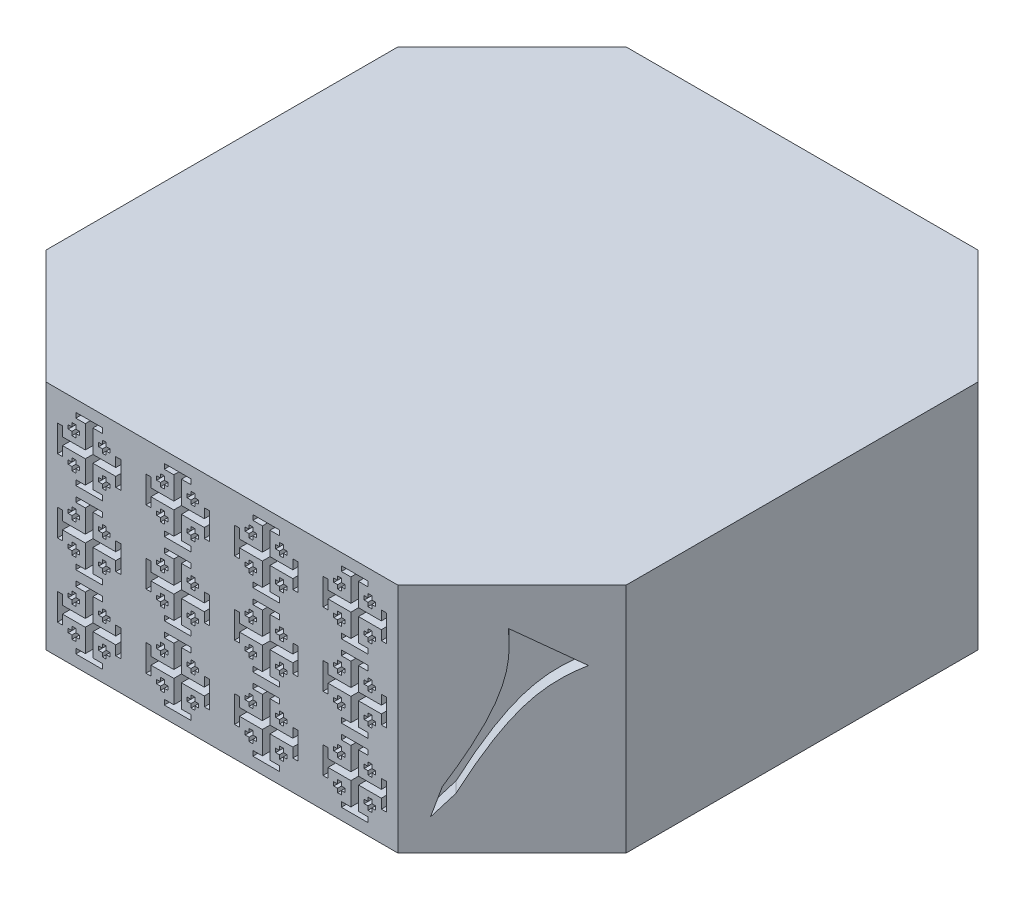
SolidWorks part; units mm, degrees
ref_plane "Front Plane" through (0, 0, 0) normal (0, 0, 1) x (1, 0, 0)
ref_plane "Top Plane" through (0, 0, 0) normal (0, 1, 0) x (1, 0, 0)
ref_plane "Right Plane" through (0, 0, 0) normal (1, 0, 0) x (0, 0, -1)
sketch "Sketch1" plane through (0, 0, 0) normal (0, 1, 0) x (1, 0, 0)
  line L1 (0, 0) -> (38.1, 0)
  line L2 (0, 0) -> (0, 38.1)
  line L3 (0, 38.1) -> (38.1, 38.1)
  line L4 (38.1, 0) -> (38.1, 38.1)
  dimension "D1" = 38.1
extrude "Boss-Extrude1" add sketch "Sketch1" along normal blind 15.24
sketch "Sketch2" plane through (0, 15.24, 0) normal (0, 1, 0) x (1, 0, 0)
  line L0 (0, 19.05) -> (38.1, 19.05) construction
  line L1 (0, 38.1) -> (0, 0) construction
  line L2 (38.1, 0) -> (38.1, 38.1) construction
  line L15 (38.1, 30.6) -> (30.6, 38.1)
  line L33 (38.1, 7.5) -> (30.6, 0)
  line L34 (7.5, 0) -> (0, 7.5)
  line L35 (7.5, 38.1) -> (0, 30.6)
  line L36 (38.1, 7.5) -> (38.1, 0)
  line L37 (38.1, 0) -> (30.6, 0)
  line L38 (38.1, 30.6) -> (38.1, 38.1)
  line L39 (38.1, 38.1) -> (30.6, 38.1)
  line L40 (7.5, 38.1) -> (0, 38.1)
  line L41 (0, 38.1) -> (0, 30.6)
  line L42 (0, 7.5) -> (0, 0)
  line L43 (0, 0) -> (7.5, 0)
  dimension "D1" = 7.5
extrude "Cut-Extrude1" cut sketch "Sketch2" against normal through all
ref_plane "Plane1" through (30.6, 0, 0) normal (1, 0, 0) x (0, 1, 0)
sketch "Sketch6" plane through (15.3, 0, 15.3) normal (0.7071, 0, 0.7071) x (0.7071, 0, -0.7071)
  line L5 (24.3455, 3.4034) -> (23.1564, 2.0557)
  line L6 (23.1564, 2.0557) -> (28.6316, 11.7194) construction
  line L7 (23.1564, 2.0557) -> (23.7012, 3.7684)
  line L8 (26.7727, 12.7726) -> (30.4906, 10.6661)
  spline S0 degree 3 poles (23.7012, 3.7684) (26.7187, 8.6625) (26.935, 10.6258) (26.7727, 12.7726) knots 0 0 0 0 1 1 1 1
  spline S1 degree 3 poles (24.3455, 3.4034) (26.9928, 8.5072) (28.5656, 9.7019) (30.4906, 10.6661) knots 0 0 0 0 1 1 1 1
  point P2 (23.2245, 2.2699)
  point P3 (28.6316, 11.7194)
extrude "Cut-Extrude2" cut sketch "Sketch6" against normal blind 1
sketch "Sketch9" plane through (0, 0, 0) normal (0, 0, 1) x (1, 0, 0)
  line L0 (9.205, 13.785) -> (9.205, 13.535)
  line L1 (9.205, 13.535) -> (8.955, 13.535)
  line L2 (8.955, 13.535) -> (8.955, 13.285)
  line L3 (8.955, 13.285) -> (9.205, 13.285)
  line L4 (9.205, 13.285) -> (9.205, 13.035)
  line L5 (9.205, 13.035) -> (9.455, 13.035)
  line L6 (9.455, 13.035) -> (9.455, 13.285)
  line L7 (9.455, 13.285) -> (9.705, 13.285)
  line L8 (9.705, 13.285) -> (9.705, 13.535)
  line L9 (9.705, 13.535) -> (9.455, 13.535)
  line L10 (9.455, 13.535) -> (9.455, 13.785)
  line L11 (9.455, 13.785) -> (9.205, 13.785)
  line L12 (10.33, 15.24) -> (10.33, 9.58) construction
  line L13 (8.7012, 12.41) -> (14.617, 12.41) construction
  line L14 (10.33, 14.49) -> (9.455, 14.49)
  line L15 (9.455, 14.49) -> (9.455, 14.16)
  line L16 (9.455, 14.16) -> (10.08, 14.16)
  line L17 (10.08, 14.16) -> (10.08, 12.66)
  line L18 (10.08, 12.66) -> (8.58, 12.66)
  line L19 (8.58, 12.66) -> (8.58, 13.285)
  line L20 (8.58, 13.285) -> (8.25, 13.285)
  line L21 (8.25, 13.285) -> (8.25, 12.41)
  line L22 (11.705, 13.285) -> (11.705, 13.535)
  line L23 (10.08, 13.41) -> (8.955, 13.41) construction
  line L24 (9.33, 12.66) -> (9.33, 13.785) construction
  line L25 (7.5, 15.24) -> (30.6, 15.24) construction
  line L26 (11.705, 13.535) -> (11.455, 13.535)
  line L27 (11.455, 13.535) -> (11.455, 13.785)
  line L28 (11.455, 13.785) -> (11.205, 13.785)
  line L29 (11.205, 13.785) -> (11.205, 13.535)
  line L30 (11.205, 13.535) -> (10.955, 13.535)
  line L31 (10.955, 13.535) -> (10.955, 13.285)
  line L32 (10.955, 13.285) -> (11.205, 13.285)
  line L33 (11.205, 13.285) -> (11.205, 13.035)
  line L34 (11.205, 13.035) -> (11.455, 13.035)
  line L35 (11.455, 13.035) -> (11.455, 13.285)
  line L36 (11.455, 13.285) -> (11.705, 13.285)
  line L37 (10.58, 12.66) -> (10.58, 14.16)
  line L38 (10.58, 14.16) -> (11.205, 14.16)
  line L39 (11.205, 14.16) -> (11.205, 14.49)
  line L40 (11.205, 14.49) -> (10.33, 14.49)
  line L41 (12.08, 12.66) -> (10.58, 12.66)
  line L42 (12.08, 13.285) -> (12.08, 12.66)
  line L43 (12.41, 13.285) -> (12.08, 13.285)
  line L44 (12.41, 12.41) -> (12.41, 13.285)
  line L45 (11.205, 11.035) -> (11.455, 11.035)
  line L46 (11.455, 11.035) -> (11.455, 11.285)
  line L47 (11.455, 11.285) -> (11.705, 11.285)
  line L48 (11.705, 11.285) -> (11.705, 11.535)
  line L49 (11.705, 11.535) -> (11.455, 11.535)
  line L50 (11.455, 11.535) -> (11.455, 11.785)
  line L51 (11.455, 11.785) -> (11.205, 11.785)
  line L52 (11.205, 11.785) -> (11.205, 11.535)
  line L53 (11.205, 11.535) -> (10.955, 11.535)
  line L54 (10.955, 11.535) -> (10.955, 11.285)
  line L55 (10.955, 11.285) -> (11.205, 11.285)
  line L56 (11.205, 11.285) -> (11.205, 11.035)
  line L57 (10.58, 12.16) -> (12.08, 12.16)
  line L58 (12.08, 12.16) -> (12.08, 11.535)
  line L59 (12.08, 11.535) -> (12.41, 11.535)
  line L60 (12.41, 11.535) -> (12.41, 12.41)
  line L61 (10.58, 10.66) -> (10.58, 12.16)
  line L62 (11.205, 10.66) -> (10.58, 10.66)
  line L63 (11.205, 10.33) -> (11.205, 10.66)
  line L64 (10.33, 10.33) -> (11.205, 10.33)
  line L65 (8.955, 11.535) -> (8.955, 11.285)
  line L66 (8.955, 11.285) -> (9.205, 11.285)
  line L67 (9.205, 11.285) -> (9.205, 11.035)
  line L68 (9.205, 11.035) -> (9.455, 11.035)
  line L69 (9.455, 11.035) -> (9.455, 11.285)
  line L70 (9.455, 11.285) -> (9.705, 11.285)
  line L71 (9.705, 11.285) -> (9.705, 11.535)
  line L72 (9.705, 11.535) -> (9.455, 11.535)
  line L73 (9.455, 11.535) -> (9.455, 11.785)
  line L74 (9.455, 11.785) -> (9.205, 11.785)
  line L75 (9.205, 11.785) -> (9.205, 11.535)
  line L76 (9.205, 11.535) -> (8.955, 11.535)
  line L77 (10.08, 12.16) -> (10.08, 10.66)
  line L78 (10.08, 10.66) -> (9.455, 10.66)
  line L79 (9.455, 10.66) -> (9.455, 10.33)
  line L80 (9.455, 10.33) -> (10.33, 10.33)
  line L81 (8.58, 12.16) -> (10.08, 12.16)
  line L82 (8.58, 11.535) -> (8.58, 12.16)
  line L83 (8.25, 11.535) -> (8.58, 11.535)
  line L84 (8.25, 12.41) -> (8.25, 11.535)
  line L85 (16.1433, 14.49) -> (15.2683, 14.49)
  line L86 (15.2683, 14.49) -> (15.2683, 14.16)
  line L87 (15.2683, 14.16) -> (15.8933, 14.16)
  line L88 (15.8933, 14.16) -> (15.8933, 12.66)
  line L89 (15.8933, 12.66) -> (14.3933, 12.66)
  line L90 (14.3933, 12.66) -> (14.3933, 13.285)
  line L91 (14.3933, 13.285) -> (14.0633, 13.285)
  line L92 (14.0633, 13.285) -> (14.0633, 12.41)
  line L93 (14.0633, 12.41) -> (14.0633, 11.535)
  line L94 (14.0633, 11.535) -> (14.3933, 11.535)
  line L95 (14.3933, 11.535) -> (14.3933, 12.16)
  line L96 (14.3933, 12.16) -> (15.8933, 12.16)
  line L97 (15.8933, 12.16) -> (15.8933, 10.66)
  line L98 (15.8933, 10.66) -> (15.2683, 10.66)
  line L99 (15.2683, 10.66) -> (15.2683, 10.33)
  line L100 (15.2683, 10.33) -> (16.1433, 10.33)
  line L101 (16.1433, 10.33) -> (17.0183, 10.33)
  line L102 (17.0183, 10.33) -> (17.0183, 10.66)
  line L103 (17.0183, 10.66) -> (16.3933, 10.66)
  line L104 (16.3933, 10.66) -> (16.3933, 12.16)
  line L105 (16.3933, 12.16) -> (17.8933, 12.16)
  line L106 (17.8933, 12.16) -> (17.8933, 11.535)
  line L107 (17.8933, 11.535) -> (18.2233, 11.535)
  line L108 (18.2233, 11.535) -> (18.2233, 12.41)
  line L109 (18.2233, 12.41) -> (18.2233, 13.285)
  line L110 (18.2233, 13.285) -> (17.8933, 13.285)
  line L111 (17.8933, 13.285) -> (17.8933, 12.66)
  line L112 (17.8933, 12.66) -> (16.3933, 12.66)
  line L113 (16.3933, 12.66) -> (16.3933, 14.16)
  line L114 (16.3933, 14.16) -> (17.0183, 14.16)
  line L115 (17.0183, 14.16) -> (17.0183, 14.49)
  line L116 (17.0183, 14.49) -> (16.1433, 14.49)
  line L117 (15.2683, 13.785) -> (15.0183, 13.785)
  line L118 (15.0183, 13.785) -> (15.0183, 13.535)
  line L119 (15.0183, 13.535) -> (14.7683, 13.535)
  line L120 (14.7683, 13.535) -> (14.7683, 13.285)
  line L121 (14.7683, 13.285) -> (15.0183, 13.285)
  line L122 (15.0183, 13.285) -> (15.0183, 13.035)
  line L123 (15.0183, 13.035) -> (15.2683, 13.035)
  line L124 (15.2683, 13.035) -> (15.2683, 13.285)
  line L125 (15.2683, 13.285) -> (15.5183, 13.285)
  line L126 (15.5183, 13.285) -> (15.5183, 13.535)
  line L127 (15.5183, 13.535) -> (15.2683, 13.535)
  line L128 (15.2683, 13.535) -> (15.2683, 13.785)
  line L129 (14.7683, 11.535) -> (14.7683, 11.285)
  line L130 (14.7683, 11.285) -> (15.0183, 11.285)
  line L131 (15.0183, 11.285) -> (15.0183, 11.035)
  line L132 (15.0183, 11.035) -> (15.2683, 11.035)
  line L133 (15.2683, 11.035) -> (15.2683, 11.285)
  line L134 (15.2683, 11.285) -> (15.5183, 11.285)
  line L135 (15.5183, 11.285) -> (15.5183, 11.535)
  line L136 (15.5183, 11.535) -> (15.2683, 11.535)
  line L137 (15.2683, 11.535) -> (15.2683, 11.785)
  line L138 (15.2683, 11.785) -> (15.0183, 11.785)
  line L139 (15.0183, 11.785) -> (15.0183, 11.535)
  line L140 (15.0183, 11.535) -> (14.7683, 11.535)
  line L141 (17.0183, 11.035) -> (17.2683, 11.035)
  line L142 (17.2683, 11.035) -> (17.2683, 11.285)
  line L143 (17.2683, 11.285) -> (17.5183, 11.285)
  line L144 (17.5183, 11.285) -> (17.5183, 11.535)
  line L145 (17.5183, 11.535) -> (17.2683, 11.535)
  line L146 (17.2683, 11.535) -> (17.2683, 11.785)
  line L147 (17.2683, 11.785) -> (17.0183, 11.785)
  line L148 (17.0183, 11.785) -> (17.0183, 11.535)
  line L149 (17.0183, 11.535) -> (16.7683, 11.535)
  line L150 (16.7683, 11.535) -> (16.7683, 11.285)
  line L151 (16.7683, 11.285) -> (17.0183, 11.285)
  line L152 (17.0183, 11.285) -> (17.0183, 11.035)
  line L153 (17.5183, 13.285) -> (17.5183, 13.535)
  line L154 (17.5183, 13.535) -> (17.2683, 13.535)
  line L155 (17.2683, 13.535) -> (17.2683, 13.785)
  line L156 (17.2683, 13.785) -> (17.0183, 13.785)
  line L157 (17.0183, 13.785) -> (17.0183, 13.535)
  line L158 (17.0183, 13.535) -> (16.7683, 13.535)
  line L159 (16.7683, 13.535) -> (16.7683, 13.285)
  line L160 (16.7683, 13.285) -> (17.0183, 13.285)
  line L161 (17.0183, 13.285) -> (17.0183, 13.035)
  line L162 (17.0183, 13.035) -> (17.2683, 13.035)
  line L163 (17.2683, 13.035) -> (17.2683, 13.285)
  line L164 (17.2683, 13.285) -> (17.5183, 13.285)
  line L165 (21.9567, 14.49) -> (21.0817, 14.49)
  line L166 (21.0817, 14.49) -> (21.0817, 14.16)
  line L167 (21.0817, 14.16) -> (21.7067, 14.16)
  line L168 (21.7067, 14.16) -> (21.7067, 12.66)
  line L169 (21.7067, 12.66) -> (20.2067, 12.66)
  line L170 (20.2067, 12.66) -> (20.2067, 13.285)
  line L171 (20.2067, 13.285) -> (19.8767, 13.285)
  line L172 (19.8767, 13.285) -> (19.8767, 12.41)
  line L173 (19.8767, 12.41) -> (19.8767, 11.535)
  line L174 (19.8767, 11.535) -> (20.2067, 11.535)
  line L175 (20.2067, 11.535) -> (20.2067, 12.16)
  line L176 (20.2067, 12.16) -> (21.7067, 12.16)
  line L177 (21.7067, 12.16) -> (21.7067, 10.66)
  line L178 (21.7067, 10.66) -> (21.0817, 10.66)
  line L179 (21.0817, 10.66) -> (21.0817, 10.33)
  line L180 (21.0817, 10.33) -> (21.9567, 10.33)
  line L181 (21.9567, 10.33) -> (22.8317, 10.33)
  line L182 (22.8317, 10.33) -> (22.8317, 10.66)
  line L183 (22.8317, 10.66) -> (22.2067, 10.66)
  line L184 (22.2067, 10.66) -> (22.2067, 12.16)
  line L185 (22.2067, 12.16) -> (23.7067, 12.16)
  line L186 (23.7067, 12.16) -> (23.7067, 11.535)
  line L187 (23.7067, 11.535) -> (24.0367, 11.535)
  line L188 (24.0367, 11.535) -> (24.0367, 12.41)
  line L189 (24.0367, 12.41) -> (24.0367, 13.285)
  line L190 (24.0367, 13.285) -> (23.7067, 13.285)
  line L191 (23.7067, 13.285) -> (23.7067, 12.66)
  line L192 (23.7067, 12.66) -> (22.2067, 12.66)
  line L193 (22.2067, 12.66) -> (22.2067, 14.16)
  line L194 (22.2067, 14.16) -> (22.8317, 14.16)
  line L195 (22.8317, 14.16) -> (22.8317, 14.49)
  line L196 (22.8317, 14.49) -> (21.9567, 14.49)
  line L197 (21.0817, 13.785) -> (20.8317, 13.785)
  line L198 (20.8317, 13.785) -> (20.8317, 13.535)
  line L199 (20.8317, 13.535) -> (20.5817, 13.535)
  line L200 (20.5817, 13.535) -> (20.5817, 13.285)
  line L201 (20.5817, 13.285) -> (20.8317, 13.285)
  line L202 (20.8317, 13.285) -> (20.8317, 13.035)
  line L203 (20.8317, 13.035) -> (21.0817, 13.035)
  line L204 (21.0817, 13.035) -> (21.0817, 13.285)
  line L205 (21.0817, 13.285) -> (21.3317, 13.285)
  line L206 (21.3317, 13.285) -> (21.3317, 13.535)
  line L207 (21.3317, 13.535) -> (21.0817, 13.535)
  line L208 (21.0817, 13.535) -> (21.0817, 13.785)
  line L209 (20.5817, 11.535) -> (20.5817, 11.285)
  line L210 (20.5817, 11.285) -> (20.8317, 11.285)
  line L211 (20.8317, 11.285) -> (20.8317, 11.035)
  line L212 (20.8317, 11.035) -> (21.0817, 11.035)
  line L213 (21.0817, 11.035) -> (21.0817, 11.285)
  line L214 (21.0817, 11.285) -> (21.3317, 11.285)
  line L215 (21.3317, 11.285) -> (21.3317, 11.535)
  line L216 (21.3317, 11.535) -> (21.0817, 11.535)
  line L217 (21.0817, 11.535) -> (21.0817, 11.785)
  line L218 (21.0817, 11.785) -> (20.8317, 11.785)
  line L219 (20.8317, 11.785) -> (20.8317, 11.535)
  line L220 (20.8317, 11.535) -> (20.5817, 11.535)
  line L221 (22.8317, 11.035) -> (23.0817, 11.035)
  line L222 (23.0817, 11.035) -> (23.0817, 11.285)
  line L223 (23.0817, 11.285) -> (23.3317, 11.285)
  line L224 (23.3317, 11.285) -> (23.3317, 11.535)
  line L225 (23.3317, 11.535) -> (23.0817, 11.535)
  line L226 (23.0817, 11.535) -> (23.0817, 11.785)
  line L227 (23.0817, 11.785) -> (22.8317, 11.785)
  line L228 (22.8317, 11.785) -> (22.8317, 11.535)
  line L229 (22.8317, 11.535) -> (22.5817, 11.535)
  line L230 (22.5817, 11.535) -> (22.5817, 11.285)
  line L231 (22.5817, 11.285) -> (22.8317, 11.285)
  line L232 (22.8317, 11.285) -> (22.8317, 11.035)
  line L233 (23.3317, 13.285) -> (23.3317, 13.535)
  line L234 (23.3317, 13.535) -> (23.0817, 13.535)
  line L235 (23.0817, 13.535) -> (23.0817, 13.785)
  line L236 (23.0817, 13.785) -> (22.8317, 13.785)
  line L237 (22.8317, 13.785) -> (22.8317, 13.535)
  line L238 (22.8317, 13.535) -> (22.5817, 13.535)
  line L239 (22.5817, 13.535) -> (22.5817, 13.285)
  line L240 (22.5817, 13.285) -> (22.8317, 13.285)
  line L241 (22.8317, 13.285) -> (22.8317, 13.035)
  line L242 (22.8317, 13.035) -> (23.0817, 13.035)
  line L243 (23.0817, 13.035) -> (23.0817, 13.285)
  line L244 (23.0817, 13.285) -> (23.3317, 13.285)
  line L245 (27.77, 14.49) -> (26.895, 14.49)
  line L246 (26.895, 14.49) -> (26.895, 14.16)
  line L247 (26.895, 14.16) -> (27.52, 14.16)
  line L248 (27.52, 14.16) -> (27.52, 12.66)
  line L249 (27.52, 12.66) -> (26.02, 12.66)
  line L250 (26.02, 12.66) -> (26.02, 13.285)
  line L251 (26.02, 13.285) -> (25.69, 13.285)
  line L252 (25.69, 13.285) -> (25.69, 12.41)
  line L253 (25.69, 12.41) -> (25.69, 11.535)
  line L254 (25.69, 11.535) -> (26.02, 11.535)
  line L255 (26.02, 11.535) -> (26.02, 12.16)
  line L256 (26.02, 12.16) -> (27.52, 12.16)
  line L257 (27.52, 12.16) -> (27.52, 10.66)
  line L258 (27.52, 10.66) -> (26.895, 10.66)
  line L259 (26.895, 10.66) -> (26.895, 10.33)
  line L260 (26.895, 10.33) -> (27.77, 10.33)
  line L261 (27.77, 10.33) -> (28.645, 10.33)
  line L262 (28.645, 10.33) -> (28.645, 10.66)
  line L263 (28.645, 10.66) -> (28.02, 10.66)
  line L264 (28.02, 10.66) -> (28.02, 12.16)
  line L265 (28.02, 12.16) -> (29.52, 12.16)
  line L266 (29.52, 12.16) -> (29.52, 11.535)
  line L267 (29.52, 11.535) -> (29.85, 11.535)
  line L268 (29.85, 11.535) -> (29.85, 12.41)
  line L269 (29.85, 12.41) -> (29.85, 13.285)
  line L270 (29.85, 13.285) -> (29.52, 13.285)
  line L271 (29.52, 13.285) -> (29.52, 12.66)
  line L272 (29.52, 12.66) -> (28.02, 12.66)
  line L273 (28.02, 12.66) -> (28.02, 14.16)
  line L274 (28.02, 14.16) -> (28.645, 14.16)
  line L275 (28.645, 14.16) -> (28.645, 14.49)
  line L276 (28.645, 14.49) -> (27.77, 14.49)
  line L277 (26.895, 13.785) -> (26.645, 13.785)
  line L278 (26.645, 13.785) -> (26.645, 13.535)
  line L279 (26.645, 13.535) -> (26.395, 13.535)
  line L280 (26.395, 13.535) -> (26.395, 13.285)
  line L281 (26.395, 13.285) -> (26.645, 13.285)
  line L282 (26.645, 13.285) -> (26.645, 13.035)
  line L283 (26.645, 13.035) -> (26.895, 13.035)
  line L284 (26.895, 13.035) -> (26.895, 13.285)
  line L285 (26.895, 13.285) -> (27.145, 13.285)
  line L286 (27.145, 13.285) -> (27.145, 13.535)
  line L287 (27.145, 13.535) -> (26.895, 13.535)
  line L288 (26.895, 13.535) -> (26.895, 13.785)
  line L289 (26.395, 11.535) -> (26.395, 11.285)
  line L290 (26.395, 11.285) -> (26.645, 11.285)
  line L291 (26.645, 11.285) -> (26.645, 11.035)
  line L292 (26.645, 11.035) -> (26.895, 11.035)
  line L293 (26.895, 11.035) -> (26.895, 11.285)
  line L294 (26.895, 11.285) -> (27.145, 11.285)
  line L295 (27.145, 11.285) -> (27.145, 11.535)
  line L296 (27.145, 11.535) -> (26.895, 11.535)
  line L297 (26.895, 11.535) -> (26.895, 11.785)
  line L298 (26.895, 11.785) -> (26.645, 11.785)
  line L299 (26.645, 11.785) -> (26.645, 11.535)
  line L300 (26.645, 11.535) -> (26.395, 11.535)
  line L301 (28.645, 11.035) -> (28.895, 11.035)
  line L302 (28.895, 11.035) -> (28.895, 11.285)
  line L303 (28.895, 11.285) -> (29.145, 11.285)
  line L304 (29.145, 11.285) -> (29.145, 11.535)
  line L305 (29.145, 11.535) -> (28.895, 11.535)
  line L306 (28.895, 11.535) -> (28.895, 11.785)
  line L307 (28.895, 11.785) -> (28.645, 11.785)
  line L308 (28.645, 11.785) -> (28.645, 11.535)
  line L309 (28.645, 11.535) -> (28.395, 11.535)
  line L310 (28.395, 11.535) -> (28.395, 11.285)
  line L311 (28.395, 11.285) -> (28.645, 11.285)
  line L312 (28.645, 11.285) -> (28.645, 11.035)
  line L313 (29.145, 13.285) -> (29.145, 13.535)
  line L314 (29.145, 13.535) -> (28.895, 13.535)
  line L315 (28.895, 13.535) -> (28.895, 13.785)
  line L316 (28.895, 13.785) -> (28.645, 13.785)
  line L317 (28.645, 13.785) -> (28.645, 13.535)
  line L318 (28.645, 13.535) -> (28.395, 13.535)
  line L319 (28.395, 13.535) -> (28.395, 13.285)
  line L320 (28.395, 13.285) -> (28.645, 13.285)
  line L321 (28.645, 13.285) -> (28.645, 13.035)
  line L322 (28.645, 13.035) -> (28.895, 13.035)
  line L323 (28.895, 13.035) -> (28.895, 13.285)
  line L324 (28.895, 13.285) -> (29.145, 13.285)
  line L325 (16.1433, 9.7) -> (15.2683, 9.7)
  line L326 (15.2683, 9.7) -> (15.2683, 9.37)
  line L327 (15.2683, 9.37) -> (15.8933, 9.37)
  line L328 (15.8933, 9.37) -> (15.8933, 7.87)
  line L329 (15.8933, 7.87) -> (14.3933, 7.87)
  line L330 (14.3933, 7.87) -> (14.3933, 8.495)
  line L331 (14.3933, 8.495) -> (14.0633, 8.495)
  line L332 (14.0633, 8.495) -> (14.0633, 7.62)
  line L333 (14.0633, 7.62) -> (14.0633, 6.745)
  line L334 (14.0633, 6.745) -> (14.3933, 6.745)
  line L335 (14.3933, 6.745) -> (14.3933, 7.37)
  line L336 (14.3933, 7.37) -> (15.8933, 7.37)
  line L337 (15.8933, 7.37) -> (15.8933, 5.87)
  line L338 (15.8933, 5.87) -> (15.2683, 5.87)
  line L339 (15.2683, 5.87) -> (15.2683, 5.54)
  line L340 (15.2683, 5.54) -> (16.1433, 5.54)
  line L341 (16.1433, 5.54) -> (17.0183, 5.54)
  line L342 (17.0183, 5.54) -> (17.0183, 5.87)
  line L343 (17.0183, 5.87) -> (16.3933, 5.87)
  line L344 (16.3933, 5.87) -> (16.3933, 7.37)
  line L345 (16.3933, 7.37) -> (17.8933, 7.37)
  line L346 (17.8933, 7.37) -> (17.8933, 6.745)
  line L347 (17.8933, 6.745) -> (18.2233, 6.745)
  line L348 (18.2233, 6.745) -> (18.2233, 7.62)
  line L349 (18.2233, 7.62) -> (18.2233, 8.495)
  line L350 (18.2233, 8.495) -> (17.8933, 8.495)
  line L351 (17.8933, 8.495) -> (17.8933, 7.87)
  line L352 (17.8933, 7.87) -> (16.3933, 7.87)
  line L353 (16.3933, 7.87) -> (16.3933, 9.37)
  line L354 (16.3933, 9.37) -> (17.0183, 9.37)
  line L355 (17.0183, 9.37) -> (17.0183, 9.7)
  line L356 (17.0183, 9.7) -> (16.1433, 9.7)
  line L357 (15.2683, 8.995) -> (15.0183, 8.995)
  line L358 (15.0183, 8.995) -> (15.0183, 8.745)
  line L359 (15.0183, 8.745) -> (14.7683, 8.745)
  line L360 (14.7683, 8.745) -> (14.7683, 8.495)
  line L361 (14.7683, 8.495) -> (15.0183, 8.495)
  line L362 (15.0183, 8.495) -> (15.0183, 8.245)
  line L363 (15.0183, 8.245) -> (15.2683, 8.245)
  line L364 (15.2683, 8.245) -> (15.2683, 8.495)
  line L365 (15.2683, 8.495) -> (15.5183, 8.495)
  line L366 (15.5183, 8.495) -> (15.5183, 8.745)
  line L367 (15.5183, 8.745) -> (15.2683, 8.745)
  line L368 (15.2683, 8.745) -> (15.2683, 8.995)
  line L369 (14.7683, 6.745) -> (14.7683, 6.495)
  line L370 (14.7683, 6.495) -> (15.0183, 6.495)
  line L371 (15.0183, 6.495) -> (15.0183, 6.245)
  line L372 (15.0183, 6.245) -> (15.2683, 6.245)
  line L373 (15.2683, 6.245) -> (15.2683, 6.495)
  line L374 (15.2683, 6.495) -> (15.5183, 6.495)
  line L375 (15.5183, 6.495) -> (15.5183, 6.745)
  line L376 (15.5183, 6.745) -> (15.2683, 6.745)
  line L377 (15.2683, 6.745) -> (15.2683, 6.995)
  line L378 (15.2683, 6.995) -> (15.0183, 6.995)
  line L379 (15.0183, 6.995) -> (15.0183, 6.745)
  line L380 (15.0183, 6.745) -> (14.7683, 6.745)
  line L381 (17.0183, 6.245) -> (17.2683, 6.245)
  line L382 (17.2683, 6.245) -> (17.2683, 6.495)
  line L383 (17.2683, 6.495) -> (17.5183, 6.495)
  line L384 (17.5183, 6.495) -> (17.5183, 6.745)
  line L385 (17.5183, 6.745) -> (17.2683, 6.745)
  line L386 (17.2683, 6.745) -> (17.2683, 6.995)
  line L387 (17.2683, 6.995) -> (17.0183, 6.995)
  line L388 (17.0183, 6.995) -> (17.0183, 6.745)
  line L389 (17.0183, 6.745) -> (16.7683, 6.745)
  line L390 (16.7683, 6.745) -> (16.7683, 6.495)
  line L391 (16.7683, 6.495) -> (17.0183, 6.495)
  line L392 (17.0183, 6.495) -> (17.0183, 6.245)
  line L393 (17.5183, 8.495) -> (17.5183, 8.745)
  line L394 (17.5183, 8.745) -> (17.2683, 8.745)
  line L395 (17.2683, 8.745) -> (17.2683, 8.995)
  line L396 (17.2683, 8.995) -> (17.0183, 8.995)
  line L397 (17.0183, 8.995) -> (17.0183, 8.745)
  line L398 (17.0183, 8.745) -> (16.7683, 8.745)
  line L399 (16.7683, 8.745) -> (16.7683, 8.495)
  line L400 (16.7683, 8.495) -> (17.0183, 8.495)
  line L401 (17.0183, 8.495) -> (17.0183, 8.245)
  line L402 (17.0183, 8.245) -> (17.2683, 8.245)
  line L403 (17.2683, 8.245) -> (17.2683, 8.495)
  line L404 (17.2683, 8.495) -> (17.5183, 8.495)
  line L405 (21.9567, 9.7) -> (21.0817, 9.7)
  line L406 (21.0817, 9.7) -> (21.0817, 9.37)
  line L407 (21.0817, 9.37) -> (21.7067, 9.37)
  line L408 (21.7067, 9.37) -> (21.7067, 7.87)
  line L409 (21.7067, 7.87) -> (20.2067, 7.87)
  line L410 (20.2067, 7.87) -> (20.2067, 8.495)
  line L411 (20.2067, 8.495) -> (19.8767, 8.495)
  line L412 (19.8767, 8.495) -> (19.8767, 7.62)
  line L413 (19.8767, 7.62) -> (19.8767, 6.745)
  line L414 (19.8767, 6.745) -> (20.2067, 6.745)
  line L415 (20.2067, 6.745) -> (20.2067, 7.37)
  line L416 (20.2067, 7.37) -> (21.7067, 7.37)
  line L417 (21.7067, 7.37) -> (21.7067, 5.87)
  line L418 (21.7067, 5.87) -> (21.0817, 5.87)
  line L419 (21.0817, 5.87) -> (21.0817, 5.54)
  line L420 (21.0817, 5.54) -> (21.9567, 5.54)
  line L421 (21.9567, 5.54) -> (22.8317, 5.54)
  line L422 (22.8317, 5.54) -> (22.8317, 5.87)
  line L423 (22.8317, 5.87) -> (22.2067, 5.87)
  line L424 (22.2067, 5.87) -> (22.2067, 7.37)
  line L425 (22.2067, 7.37) -> (23.7067, 7.37)
  line L426 (23.7067, 7.37) -> (23.7067, 6.745)
  line L427 (23.7067, 6.745) -> (24.0367, 6.745)
  line L428 (24.0367, 6.745) -> (24.0367, 7.62)
  line L429 (24.0367, 7.62) -> (24.0367, 8.495)
  line L430 (24.0367, 8.495) -> (23.7067, 8.495)
  line L431 (23.7067, 8.495) -> (23.7067, 7.87)
  line L432 (23.7067, 7.87) -> (22.2067, 7.87)
  line L433 (22.2067, 7.87) -> (22.2067, 9.37)
  line L434 (22.2067, 9.37) -> (22.8317, 9.37)
  line L435 (22.8317, 9.37) -> (22.8317, 9.7)
  line L436 (22.8317, 9.7) -> (21.9567, 9.7)
  line L437 (21.0817, 8.995) -> (20.8317, 8.995)
  line L438 (20.8317, 8.995) -> (20.8317, 8.745)
  line L439 (20.8317, 8.745) -> (20.5817, 8.745)
  line L440 (20.5817, 8.745) -> (20.5817, 8.495)
  line L441 (20.5817, 8.495) -> (20.8317, 8.495)
  line L442 (20.8317, 8.495) -> (20.8317, 8.245)
  line L443 (20.8317, 8.245) -> (21.0817, 8.245)
  line L444 (21.0817, 8.245) -> (21.0817, 8.495)
  line L445 (21.0817, 8.495) -> (21.3317, 8.495)
  line L446 (21.3317, 8.495) -> (21.3317, 8.745)
  line L447 (21.3317, 8.745) -> (21.0817, 8.745)
  line L448 (21.0817, 8.745) -> (21.0817, 8.995)
  line L449 (20.5817, 6.745) -> (20.5817, 6.495)
  line L450 (20.5817, 6.495) -> (20.8317, 6.495)
  line L451 (20.8317, 6.495) -> (20.8317, 6.245)
  line L452 (20.8317, 6.245) -> (21.0817, 6.245)
  line L453 (21.0817, 6.245) -> (21.0817, 6.495)
  line L454 (21.0817, 6.495) -> (21.3317, 6.495)
  line L455 (21.3317, 6.495) -> (21.3317, 6.745)
  line L456 (21.3317, 6.745) -> (21.0817, 6.745)
  line L457 (21.0817, 6.745) -> (21.0817, 6.995)
  line L458 (21.0817, 6.995) -> (20.8317, 6.995)
  line L459 (20.8317, 6.995) -> (20.8317, 6.745)
  line L460 (20.8317, 6.745) -> (20.5817, 6.745)
  line L461 (22.8317, 6.245) -> (23.0817, 6.245)
  line L462 (23.0817, 6.245) -> (23.0817, 6.495)
  line L463 (23.0817, 6.495) -> (23.3317, 6.495)
  line L464 (23.3317, 6.495) -> (23.3317, 6.745)
  line L465 (23.3317, 6.745) -> (23.0817, 6.745)
  line L466 (23.0817, 6.745) -> (23.0817, 6.995)
  line L467 (23.0817, 6.995) -> (22.8317, 6.995)
  line L468 (22.8317, 6.995) -> (22.8317, 6.745)
  line L469 (22.8317, 6.745) -> (22.5817, 6.745)
  line L470 (22.5817, 6.745) -> (22.5817, 6.495)
  line L471 (22.5817, 6.495) -> (22.8317, 6.495)
  line L472 (22.8317, 6.495) -> (22.8317, 6.245)
  line L473 (23.3317, 8.495) -> (23.3317, 8.745)
  line L474 (23.3317, 8.745) -> (23.0817, 8.745)
  line L475 (23.0817, 8.745) -> (23.0817, 8.995)
  line L476 (23.0817, 8.995) -> (22.8317, 8.995)
  line L477 (22.8317, 8.995) -> (22.8317, 8.745)
  line L478 (22.8317, 8.745) -> (22.5817, 8.745)
  line L479 (22.5817, 8.745) -> (22.5817, 8.495)
  line L480 (22.5817, 8.495) -> (22.8317, 8.495)
  line L481 (22.8317, 8.495) -> (22.8317, 8.245)
  line L482 (22.8317, 8.245) -> (23.0817, 8.245)
  line L483 (23.0817, 8.245) -> (23.0817, 8.495)
  line L484 (23.0817, 8.495) -> (23.3317, 8.495)
  line L485 (27.77, 9.7) -> (26.895, 9.7)
  line L486 (26.895, 9.7) -> (26.895, 9.37)
  line L487 (26.895, 9.37) -> (27.52, 9.37)
  line L488 (27.52, 9.37) -> (27.52, 7.87)
  line L489 (27.52, 7.87) -> (26.02, 7.87)
  line L490 (26.02, 7.87) -> (26.02, 8.495)
  line L491 (26.02, 8.495) -> (25.69, 8.495)
  line L492 (25.69, 8.495) -> (25.69, 7.62)
  line L493 (25.69, 7.62) -> (25.69, 6.745)
  line L494 (25.69, 6.745) -> (26.02, 6.745)
  line L495 (26.02, 6.745) -> (26.02, 7.37)
  line L496 (26.02, 7.37) -> (27.52, 7.37)
  line L497 (27.52, 7.37) -> (27.52, 5.87)
  line L498 (27.52, 5.87) -> (26.895, 5.87)
  line L499 (26.895, 5.87) -> (26.895, 5.54)
  line L500 (26.895, 5.54) -> (27.77, 5.54)
  line L501 (27.77, 5.54) -> (28.645, 5.54)
  line L502 (28.645, 5.54) -> (28.645, 5.87)
  line L503 (28.645, 5.87) -> (28.02, 5.87)
  line L504 (28.02, 5.87) -> (28.02, 7.37)
  line L505 (28.02, 7.37) -> (29.52, 7.37)
  line L506 (29.52, 7.37) -> (29.52, 6.745)
  line L507 (29.52, 6.745) -> (29.85, 6.745)
  line L508 (29.85, 6.745) -> (29.85, 7.62)
  line L509 (29.85, 7.62) -> (29.85, 8.495)
  line L510 (29.85, 8.495) -> (29.52, 8.495)
  line L511 (29.52, 8.495) -> (29.52, 7.87)
  line L512 (29.52, 7.87) -> (28.02, 7.87)
  line L513 (28.02, 7.87) -> (28.02, 9.37)
  line L514 (28.02, 9.37) -> (28.645, 9.37)
  line L515 (28.645, 9.37) -> (28.645, 9.7)
  line L516 (28.645, 9.7) -> (27.77, 9.7)
  line L517 (26.895, 8.995) -> (26.645, 8.995)
  line L518 (26.645, 8.995) -> (26.645, 8.745)
  line L519 (26.645, 8.745) -> (26.395, 8.745)
  line L520 (26.395, 8.745) -> (26.395, 8.495)
  line L521 (26.395, 8.495) -> (26.645, 8.495)
  line L522 (26.645, 8.495) -> (26.645, 8.245)
  line L523 (26.645, 8.245) -> (26.895, 8.245)
  line L524 (26.895, 8.245) -> (26.895, 8.495)
  line L525 (26.895, 8.495) -> (27.145, 8.495)
  line L526 (27.145, 8.495) -> (27.145, 8.745)
  line L527 (27.145, 8.745) -> (26.895, 8.745)
  line L528 (26.895, 8.745) -> (26.895, 8.995)
  line L529 (26.395, 6.745) -> (26.395, 6.495)
  line L530 (26.395, 6.495) -> (26.645, 6.495)
  line L531 (26.645, 6.495) -> (26.645, 6.245)
  line L532 (26.645, 6.245) -> (26.895, 6.245)
  line L533 (26.895, 6.245) -> (26.895, 6.495)
  line L534 (26.895, 6.495) -> (27.145, 6.495)
  line L535 (27.145, 6.495) -> (27.145, 6.745)
  line L536 (27.145, 6.745) -> (26.895, 6.745)
  line L537 (26.895, 6.745) -> (26.895, 6.995)
  line L538 (26.895, 6.995) -> (26.645, 6.995)
  line L539 (26.645, 6.995) -> (26.645, 6.745)
  line L540 (26.645, 6.745) -> (26.395, 6.745)
  line L541 (28.645, 6.245) -> (28.895, 6.245)
  line L542 (28.895, 6.245) -> (28.895, 6.495)
  line L543 (28.895, 6.495) -> (29.145, 6.495)
  line L544 (29.145, 6.495) -> (29.145, 6.745)
  line L545 (29.145, 6.745) -> (28.895, 6.745)
  line L546 (28.895, 6.745) -> (28.895, 6.995)
  line L547 (28.895, 6.995) -> (28.645, 6.995)
  line L548 (28.645, 6.995) -> (28.645, 6.745)
  line L549 (28.645, 6.745) -> (28.395, 6.745)
  line L550 (28.395, 6.745) -> (28.395, 6.495)
  line L551 (28.395, 6.495) -> (28.645, 6.495)
  line L552 (28.645, 6.495) -> (28.645, 6.245)
  line L553 (29.145, 8.495) -> (29.145, 8.745)
  line L554 (29.145, 8.745) -> (28.895, 8.745)
  line L555 (28.895, 8.745) -> (28.895, 8.995)
  line L556 (28.895, 8.995) -> (28.645, 8.995)
  line L557 (28.645, 8.995) -> (28.645, 8.745)
  line L558 (28.645, 8.745) -> (28.395, 8.745)
  line L559 (28.395, 8.745) -> (28.395, 8.495)
  line L560 (28.395, 8.495) -> (28.645, 8.495)
  line L561 (28.645, 8.495) -> (28.645, 8.245)
  line L562 (28.645, 8.245) -> (28.895, 8.245)
  line L563 (28.895, 8.245) -> (28.895, 8.495)
  line L564 (28.895, 8.495) -> (29.145, 8.495)
  line L565 (16.1433, 4.91) -> (15.2683, 4.91)
  line L566 (15.2683, 4.91) -> (15.2683, 4.58)
  line L567 (15.2683, 4.58) -> (15.8933, 4.58)
  line L568 (15.8933, 4.58) -> (15.8933, 3.08)
  line L569 (15.8933, 3.08) -> (14.3933, 3.08)
  line L570 (14.3933, 3.08) -> (14.3933, 3.705)
  line L571 (14.3933, 3.705) -> (14.0633, 3.705)
  line L572 (14.0633, 3.705) -> (14.0633, 2.83)
  line L573 (14.0633, 2.83) -> (14.0633, 1.955)
  line L574 (14.0633, 1.955) -> (14.3933, 1.955)
  line L575 (14.3933, 1.955) -> (14.3933, 2.58)
  line L576 (14.3933, 2.58) -> (15.8933, 2.58)
  line L577 (15.8933, 2.58) -> (15.8933, 1.08)
  line L578 (15.8933, 1.08) -> (15.2683, 1.08)
  line L579 (15.2683, 1.08) -> (15.2683, 0.75)
  line L580 (15.2683, 0.75) -> (16.1433, 0.75)
  line L581 (16.1433, 0.75) -> (17.0183, 0.75)
  line L582 (17.0183, 0.75) -> (17.0183, 1.08)
  line L583 (17.0183, 1.08) -> (16.3933, 1.08)
  line L584 (16.3933, 1.08) -> (16.3933, 2.58)
  line L585 (16.3933, 2.58) -> (17.8933, 2.58)
  line L586 (17.8933, 2.58) -> (17.8933, 1.955)
  line L587 (17.8933, 1.955) -> (18.2233, 1.955)
  line L588 (18.2233, 1.955) -> (18.2233, 2.83)
  line L589 (18.2233, 2.83) -> (18.2233, 3.705)
  line L590 (18.2233, 3.705) -> (17.8933, 3.705)
  line L591 (17.8933, 3.705) -> (17.8933, 3.08)
  line L592 (17.8933, 3.08) -> (16.3933, 3.08)
  line L593 (16.3933, 3.08) -> (16.3933, 4.58)
  line L594 (16.3933, 4.58) -> (17.0183, 4.58)
  line L595 (17.0183, 4.58) -> (17.0183, 4.91)
  line L596 (17.0183, 4.91) -> (16.1433, 4.91)
  line L597 (15.2683, 4.205) -> (15.0183, 4.205)
  line L598 (15.0183, 4.205) -> (15.0183, 3.955)
  line L599 (15.0183, 3.955) -> (14.7683, 3.955)
  line L600 (14.7683, 3.955) -> (14.7683, 3.705)
  line L601 (14.7683, 3.705) -> (15.0183, 3.705)
  line L602 (15.0183, 3.705) -> (15.0183, 3.455)
  line L603 (15.0183, 3.455) -> (15.2683, 3.455)
  line L604 (15.2683, 3.455) -> (15.2683, 3.705)
  line L605 (15.2683, 3.705) -> (15.5183, 3.705)
  line L606 (15.5183, 3.705) -> (15.5183, 3.955)
  line L607 (15.5183, 3.955) -> (15.2683, 3.955)
  line L608 (15.2683, 3.955) -> (15.2683, 4.205)
  line L609 (14.7683, 1.955) -> (14.7683, 1.705)
  line L610 (14.7683, 1.705) -> (15.0183, 1.705)
  line L611 (15.0183, 1.705) -> (15.0183, 1.455)
  line L612 (15.0183, 1.455) -> (15.2683, 1.455)
  line L613 (15.2683, 1.455) -> (15.2683, 1.705)
  line L614 (15.2683, 1.705) -> (15.5183, 1.705)
  line L615 (15.5183, 1.705) -> (15.5183, 1.955)
  line L616 (15.5183, 1.955) -> (15.2683, 1.955)
  line L617 (15.2683, 1.955) -> (15.2683, 2.205)
  line L618 (15.2683, 2.205) -> (15.0183, 2.205)
  line L619 (15.0183, 2.205) -> (15.0183, 1.955)
  line L620 (15.0183, 1.955) -> (14.7683, 1.955)
  line L621 (17.0183, 1.455) -> (17.2683, 1.455)
  line L622 (17.2683, 1.455) -> (17.2683, 1.705)
  line L623 (17.2683, 1.705) -> (17.5183, 1.705)
  line L624 (17.5183, 1.705) -> (17.5183, 1.955)
  line L625 (17.5183, 1.955) -> (17.2683, 1.955)
  line L626 (17.2683, 1.955) -> (17.2683, 2.205)
  line L627 (17.2683, 2.205) -> (17.0183, 2.205)
  line L628 (17.0183, 2.205) -> (17.0183, 1.955)
  line L629 (17.0183, 1.955) -> (16.7683, 1.955)
  line L630 (16.7683, 1.955) -> (16.7683, 1.705)
  line L631 (16.7683, 1.705) -> (17.0183, 1.705)
  line L632 (17.0183, 1.705) -> (17.0183, 1.455)
  line L633 (17.5183, 3.705) -> (17.5183, 3.955)
  line L634 (17.5183, 3.955) -> (17.2683, 3.955)
  line L635 (17.2683, 3.955) -> (17.2683, 4.205)
  line L636 (17.2683, 4.205) -> (17.0183, 4.205)
  line L637 (17.0183, 4.205) -> (17.0183, 3.955)
  line L638 (17.0183, 3.955) -> (16.7683, 3.955)
  line L639 (16.7683, 3.955) -> (16.7683, 3.705)
  line L640 (16.7683, 3.705) -> (17.0183, 3.705)
  line L641 (17.0183, 3.705) -> (17.0183, 3.455)
  line L642 (17.0183, 3.455) -> (17.2683, 3.455)
  line L643 (17.2683, 3.455) -> (17.2683, 3.705)
  line L644 (17.2683, 3.705) -> (17.5183, 3.705)
  line L645 (21.9567, 4.91) -> (21.0817, 4.91)
  line L646 (21.0817, 4.91) -> (21.0817, 4.58)
  line L647 (21.0817, 4.58) -> (21.7067, 4.58)
  line L648 (21.7067, 4.58) -> (21.7067, 3.08)
  line L649 (21.7067, 3.08) -> (20.2067, 3.08)
  line L650 (20.2067, 3.08) -> (20.2067, 3.705)
  line L651 (20.2067, 3.705) -> (19.8767, 3.705)
  line L652 (19.8767, 3.705) -> (19.8767, 2.83)
  line L653 (19.8767, 2.83) -> (19.8767, 1.955)
  line L654 (19.8767, 1.955) -> (20.2067, 1.955)
  line L655 (20.2067, 1.955) -> (20.2067, 2.58)
  line L656 (20.2067, 2.58) -> (21.7067, 2.58)
  line L657 (21.7067, 2.58) -> (21.7067, 1.08)
  line L658 (21.7067, 1.08) -> (21.0817, 1.08)
  line L659 (21.0817, 1.08) -> (21.0817, 0.75)
  line L660 (21.0817, 0.75) -> (21.9567, 0.75)
  line L661 (21.9567, 0.75) -> (22.8317, 0.75)
  line L662 (22.8317, 0.75) -> (22.8317, 1.08)
  line L663 (22.8317, 1.08) -> (22.2067, 1.08)
  line L664 (22.2067, 1.08) -> (22.2067, 2.58)
  line L665 (22.2067, 2.58) -> (23.7067, 2.58)
  line L666 (23.7067, 2.58) -> (23.7067, 1.955)
  line L667 (23.7067, 1.955) -> (24.0367, 1.955)
  line L668 (24.0367, 1.955) -> (24.0367, 2.83)
  line L669 (24.0367, 2.83) -> (24.0367, 3.705)
  line L670 (24.0367, 3.705) -> (23.7067, 3.705)
  line L671 (23.7067, 3.705) -> (23.7067, 3.08)
  line L672 (23.7067, 3.08) -> (22.2067, 3.08)
  line L673 (22.2067, 3.08) -> (22.2067, 4.58)
  line L674 (22.2067, 4.58) -> (22.8317, 4.58)
  line L675 (22.8317, 4.58) -> (22.8317, 4.91)
  line L676 (22.8317, 4.91) -> (21.9567, 4.91)
  line L677 (21.0817, 4.205) -> (20.8317, 4.205)
  line L678 (20.8317, 4.205) -> (20.8317, 3.955)
  line L679 (20.8317, 3.955) -> (20.5817, 3.955)
  line L680 (20.5817, 3.955) -> (20.5817, 3.705)
  line L681 (20.5817, 3.705) -> (20.8317, 3.705)
  line L682 (20.8317, 3.705) -> (20.8317, 3.455)
  line L683 (20.8317, 3.455) -> (21.0817, 3.455)
  line L684 (21.0817, 3.455) -> (21.0817, 3.705)
  line L685 (21.0817, 3.705) -> (21.3317, 3.705)
  line L686 (21.3317, 3.705) -> (21.3317, 3.955)
  line L687 (21.3317, 3.955) -> (21.0817, 3.955)
  line L688 (21.0817, 3.955) -> (21.0817, 4.205)
  line L689 (20.5817, 1.955) -> (20.5817, 1.705)
  line L690 (20.5817, 1.705) -> (20.8317, 1.705)
  line L691 (20.8317, 1.705) -> (20.8317, 1.455)
  line L692 (20.8317, 1.455) -> (21.0817, 1.455)
  line L693 (21.0817, 1.455) -> (21.0817, 1.705)
  line L694 (21.0817, 1.705) -> (21.3317, 1.705)
  line L695 (21.3317, 1.705) -> (21.3317, 1.955)
  line L696 (21.3317, 1.955) -> (21.0817, 1.955)
  line L697 (21.0817, 1.955) -> (21.0817, 2.205)
  line L698 (21.0817, 2.205) -> (20.8317, 2.205)
  line L699 (20.8317, 2.205) -> (20.8317, 1.955)
  line L700 (20.8317, 1.955) -> (20.5817, 1.955)
  line L701 (22.8317, 1.455) -> (23.0817, 1.455)
  line L702 (23.0817, 1.455) -> (23.0817, 1.705)
  line L703 (23.0817, 1.705) -> (23.3317, 1.705)
  line L704 (23.3317, 1.705) -> (23.3317, 1.955)
  line L705 (23.3317, 1.955) -> (23.0817, 1.955)
  line L706 (23.0817, 1.955) -> (23.0817, 2.205)
  line L707 (23.0817, 2.205) -> (22.8317, 2.205)
  line L708 (22.8317, 2.205) -> (22.8317, 1.955)
  line L709 (22.8317, 1.955) -> (22.5817, 1.955)
  line L710 (22.5817, 1.955) -> (22.5817, 1.705)
  line L711 (22.5817, 1.705) -> (22.8317, 1.705)
  line L712 (22.8317, 1.705) -> (22.8317, 1.455)
  line L713 (23.3317, 3.705) -> (23.3317, 3.955)
  line L714 (23.3317, 3.955) -> (23.0817, 3.955)
  line L715 (23.0817, 3.955) -> (23.0817, 4.205)
  line L716 (23.0817, 4.205) -> (22.8317, 4.205)
  line L717 (22.8317, 4.205) -> (22.8317, 3.955)
  line L718 (22.8317, 3.955) -> (22.5817, 3.955)
  line L719 (22.5817, 3.955) -> (22.5817, 3.705)
  line L720 (22.5817, 3.705) -> (22.8317, 3.705)
  line L721 (22.8317, 3.705) -> (22.8317, 3.455)
  line L722 (22.8317, 3.455) -> (23.0817, 3.455)
  line L723 (23.0817, 3.455) -> (23.0817, 3.705)
  line L724 (23.0817, 3.705) -> (23.3317, 3.705)
  line L725 (27.77, 4.91) -> (26.895, 4.91)
  line L726 (26.895, 4.91) -> (26.895, 4.58)
  line L727 (26.895, 4.58) -> (27.52, 4.58)
  line L728 (27.52, 4.58) -> (27.52, 3.08)
  line L729 (27.52, 3.08) -> (26.02, 3.08)
  line L730 (26.02, 3.08) -> (26.02, 3.705)
  line L731 (26.02, 3.705) -> (25.69, 3.705)
  line L732 (25.69, 3.705) -> (25.69, 2.83)
  line L733 (25.69, 2.83) -> (25.69, 1.955)
  line L734 (25.69, 1.955) -> (26.02, 1.955)
  line L735 (26.02, 1.955) -> (26.02, 2.58)
  line L736 (26.02, 2.58) -> (27.52, 2.58)
  line L737 (27.52, 2.58) -> (27.52, 1.08)
  line L738 (27.52, 1.08) -> (26.895, 1.08)
  line L739 (26.895, 1.08) -> (26.895, 0.75)
  line L740 (26.895, 0.75) -> (27.77, 0.75)
  line L741 (27.77, 0.75) -> (28.645, 0.75)
  line L742 (28.645, 0.75) -> (28.645, 1.08)
  line L743 (28.645, 1.08) -> (28.02, 1.08)
  line L744 (28.02, 1.08) -> (28.02, 2.58)
  line L745 (28.02, 2.58) -> (29.52, 2.58)
  line L746 (29.52, 2.58) -> (29.52, 1.955)
  line L747 (29.52, 1.955) -> (29.85, 1.955)
  line L748 (29.85, 1.955) -> (29.85, 2.83)
  line L749 (29.85, 2.83) -> (29.85, 3.705)
  line L750 (29.85, 3.705) -> (29.52, 3.705)
  line L751 (29.52, 3.705) -> (29.52, 3.08)
  line L752 (29.52, 3.08) -> (28.02, 3.08)
  line L753 (28.02, 3.08) -> (28.02, 4.58)
  line L754 (28.02, 4.58) -> (28.645, 4.58)
  line L755 (28.645, 4.58) -> (28.645, 4.91)
  line L756 (28.645, 4.91) -> (27.77, 4.91)
  line L757 (26.895, 4.205) -> (26.645, 4.205)
  line L758 (26.645, 4.205) -> (26.645, 3.955)
  line L759 (26.645, 3.955) -> (26.395, 3.955)
  line L760 (26.395, 3.955) -> (26.395, 3.705)
  line L761 (26.395, 3.705) -> (26.645, 3.705)
  line L762 (26.645, 3.705) -> (26.645, 3.455)
  line L763 (26.645, 3.455) -> (26.895, 3.455)
  line L764 (26.895, 3.455) -> (26.895, 3.705)
  line L765 (26.895, 3.705) -> (27.145, 3.705)
  line L766 (27.145, 3.705) -> (27.145, 3.955)
  line L767 (27.145, 3.955) -> (26.895, 3.955)
  line L768 (26.895, 3.955) -> (26.895, 4.205)
  line L769 (26.395, 1.955) -> (26.395, 1.705)
  line L770 (26.395, 1.705) -> (26.645, 1.705)
  line L771 (26.645, 1.705) -> (26.645, 1.455)
  line L772 (26.645, 1.455) -> (26.895, 1.455)
  line L773 (26.895, 1.455) -> (26.895, 1.705)
  line L774 (26.895, 1.705) -> (27.145, 1.705)
  line L775 (27.145, 1.705) -> (27.145, 1.955)
  line L776 (27.145, 1.955) -> (26.895, 1.955)
  line L777 (26.895, 1.955) -> (26.895, 2.205)
  line L778 (26.895, 2.205) -> (26.645, 2.205)
  line L779 (26.645, 2.205) -> (26.645, 1.955)
  line L780 (26.645, 1.955) -> (26.395, 1.955)
  line L781 (28.645, 1.455) -> (28.895, 1.455)
  line L782 (28.895, 1.455) -> (28.895, 1.705)
  line L783 (28.895, 1.705) -> (29.145, 1.705)
  line L784 (29.145, 1.705) -> (29.145, 1.955)
  line L785 (29.145, 1.955) -> (28.895, 1.955)
  line L786 (28.895, 1.955) -> (28.895, 2.205)
  line L787 (28.895, 2.205) -> (28.645, 2.205)
  line L788 (28.645, 2.205) -> (28.645, 1.955)
  line L789 (28.645, 1.955) -> (28.395, 1.955)
  line L790 (28.395, 1.955) -> (28.395, 1.705)
  line L791 (28.395, 1.705) -> (28.645, 1.705)
  line L792 (28.645, 1.705) -> (28.645, 1.455)
  line L793 (29.145, 3.705) -> (29.145, 3.955)
  line L794 (29.145, 3.955) -> (28.895, 3.955)
  line L795 (28.895, 3.955) -> (28.895, 4.205)
  line L796 (28.895, 4.205) -> (28.645, 4.205)
  line L797 (28.645, 4.205) -> (28.645, 3.955)
  line L798 (28.645, 3.955) -> (28.395, 3.955)
  line L799 (28.395, 3.955) -> (28.395, 3.705)
  line L800 (28.395, 3.705) -> (28.645, 3.705)
  line L801 (28.645, 3.705) -> (28.645, 3.455)
  line L802 (28.645, 3.455) -> (28.895, 3.455)
  line L803 (28.895, 3.455) -> (28.895, 3.705)
  line L804 (28.895, 3.705) -> (29.145, 3.705)
  line L805 (10.33, 9.7) -> (9.455, 9.7)
  line L806 (9.455, 9.7) -> (9.455, 9.37)
  line L807 (9.455, 9.37) -> (10.08, 9.37)
  line L808 (10.08, 9.37) -> (10.08, 7.87)
  line L809 (10.08, 7.87) -> (8.58, 7.87)
  line L810 (8.58, 7.87) -> (8.58, 8.495)
  line L811 (8.58, 8.495) -> (8.25, 8.495)
  line L812 (8.25, 8.495) -> (8.25, 7.62)
  line L813 (8.25, 7.62) -> (8.25, 6.745)
  line L814 (8.25, 6.745) -> (8.58, 6.745)
  line L815 (8.58, 6.745) -> (8.58, 7.37)
  line L816 (8.58, 7.37) -> (10.08, 7.37)
  line L817 (10.08, 7.37) -> (10.08, 5.87)
  line L818 (10.08, 5.87) -> (9.455, 5.87)
  line L819 (9.455, 5.87) -> (9.455, 5.54)
  line L820 (9.455, 5.54) -> (10.33, 5.54)
  line L821 (10.33, 5.54) -> (11.205, 5.54)
  line L822 (11.205, 5.54) -> (11.205, 5.87)
  line L823 (11.205, 5.87) -> (10.58, 5.87)
  line L824 (10.58, 5.87) -> (10.58, 7.37)
  line L825 (10.58, 7.37) -> (12.08, 7.37)
  line L826 (12.08, 7.37) -> (12.08, 6.745)
  line L827 (12.08, 6.745) -> (12.41, 6.745)
  line L828 (12.41, 6.745) -> (12.41, 7.62)
  line L829 (12.41, 7.62) -> (12.41, 8.495)
  line L830 (12.41, 8.495) -> (12.08, 8.495)
  line L831 (12.08, 8.495) -> (12.08, 7.87)
  line L832 (12.08, 7.87) -> (10.58, 7.87)
  line L833 (10.58, 7.87) -> (10.58, 9.37)
  line L834 (10.58, 9.37) -> (11.205, 9.37)
  line L835 (11.205, 9.37) -> (11.205, 9.7)
  line L836 (11.205, 9.7) -> (10.33, 9.7)
  line L837 (9.455, 8.995) -> (9.205, 8.995)
  line L838 (9.205, 8.995) -> (9.205, 8.745)
  line L839 (9.205, 8.745) -> (8.955, 8.745)
  line L840 (8.955, 8.745) -> (8.955, 8.495)
  line L841 (8.955, 8.495) -> (9.205, 8.495)
  line L842 (9.205, 8.495) -> (9.205, 8.245)
  line L843 (9.205, 8.245) -> (9.455, 8.245)
  line L844 (9.455, 8.245) -> (9.455, 8.495)
  line L845 (9.455, 8.495) -> (9.705, 8.495)
  line L846 (9.705, 8.495) -> (9.705, 8.745)
  line L847 (9.705, 8.745) -> (9.455, 8.745)
  line L848 (9.455, 8.745) -> (9.455, 8.995)
  line L849 (8.955, 6.745) -> (8.955, 6.495)
  line L850 (8.955, 6.495) -> (9.205, 6.495)
  line L851 (9.205, 6.495) -> (9.205, 6.245)
  line L852 (9.205, 6.245) -> (9.455, 6.245)
  line L853 (9.455, 6.245) -> (9.455, 6.495)
  line L854 (9.455, 6.495) -> (9.705, 6.495)
  line L855 (9.705, 6.495) -> (9.705, 6.745)
  line L856 (9.705, 6.745) -> (9.455, 6.745)
  line L857 (9.455, 6.745) -> (9.455, 6.995)
  line L858 (9.455, 6.995) -> (9.205, 6.995)
  line L859 (9.205, 6.995) -> (9.205, 6.745)
  line L860 (9.205, 6.745) -> (8.955, 6.745)
  line L861 (11.205, 6.245) -> (11.455, 6.245)
  line L862 (11.455, 6.245) -> (11.455, 6.495)
  line L863 (11.455, 6.495) -> (11.705, 6.495)
  line L864 (11.705, 6.495) -> (11.705, 6.745)
  line L865 (11.705, 6.745) -> (11.455, 6.745)
  line L866 (11.455, 6.745) -> (11.455, 6.995)
  line L867 (11.455, 6.995) -> (11.205, 6.995)
  line L868 (11.205, 6.995) -> (11.205, 6.745)
  line L869 (11.205, 6.745) -> (10.955, 6.745)
  line L870 (10.955, 6.745) -> (10.955, 6.495)
  line L871 (10.955, 6.495) -> (11.205, 6.495)
  line L872 (11.205, 6.495) -> (11.205, 6.245)
  line L873 (11.705, 8.495) -> (11.705, 8.745)
  line L874 (11.705, 8.745) -> (11.455, 8.745)
  line L875 (11.455, 8.745) -> (11.455, 8.995)
  line L876 (11.455, 8.995) -> (11.205, 8.995)
  line L877 (11.205, 8.995) -> (11.205, 8.745)
  line L878 (11.205, 8.745) -> (10.955, 8.745)
  line L879 (10.955, 8.745) -> (10.955, 8.495)
  line L880 (10.955, 8.495) -> (11.205, 8.495)
  line L881 (11.205, 8.495) -> (11.205, 8.245)
  line L882 (11.205, 8.245) -> (11.455, 8.245)
  line L883 (11.455, 8.245) -> (11.455, 8.495)
  line L884 (11.455, 8.495) -> (11.705, 8.495)
  line L885 (10.33, 4.91) -> (9.455, 4.91)
  line L886 (9.455, 4.91) -> (9.455, 4.58)
  line L887 (9.455, 4.58) -> (10.08, 4.58)
  line L888 (10.08, 4.58) -> (10.08, 3.08)
  line L889 (10.08, 3.08) -> (8.58, 3.08)
  line L890 (8.58, 3.08) -> (8.58, 3.705)
  line L891 (8.58, 3.705) -> (8.25, 3.705)
  line L892 (8.25, 3.705) -> (8.25, 2.83)
  line L893 (8.25, 2.83) -> (8.25, 1.955)
  line L894 (8.25, 1.955) -> (8.58, 1.955)
  line L895 (8.58, 1.955) -> (8.58, 2.58)
  line L896 (8.58, 2.58) -> (10.08, 2.58)
  line L897 (10.08, 2.58) -> (10.08, 1.08)
  line L898 (10.08, 1.08) -> (9.455, 1.08)
  line L899 (9.455, 1.08) -> (9.455, 0.75)
  line L900 (9.455, 0.75) -> (10.33, 0.75)
  line L901 (10.33, 0.75) -> (11.205, 0.75)
  line L902 (11.205, 0.75) -> (11.205, 1.08)
  line L903 (11.205, 1.08) -> (10.58, 1.08)
  line L904 (10.58, 1.08) -> (10.58, 2.58)
  line L905 (10.58, 2.58) -> (12.08, 2.58)
  line L906 (12.08, 2.58) -> (12.08, 1.955)
  line L907 (12.08, 1.955) -> (12.41, 1.955)
  line L908 (12.41, 1.955) -> (12.41, 2.83)
  line L909 (12.41, 2.83) -> (12.41, 3.705)
  line L910 (12.41, 3.705) -> (12.08, 3.705)
  line L911 (12.08, 3.705) -> (12.08, 3.08)
  line L912 (12.08, 3.08) -> (10.58, 3.08)
  line L913 (10.58, 3.08) -> (10.58, 4.58)
  line L914 (10.58, 4.58) -> (11.205, 4.58)
  line L915 (11.205, 4.58) -> (11.205, 4.91)
  line L916 (11.205, 4.91) -> (10.33, 4.91)
  line L917 (9.455, 4.205) -> (9.205, 4.205)
  line L918 (9.205, 4.205) -> (9.205, 3.955)
  line L919 (9.205, 3.955) -> (8.955, 3.955)
  line L920 (8.955, 3.955) -> (8.955, 3.705)
  line L921 (8.955, 3.705) -> (9.205, 3.705)
  line L922 (9.205, 3.705) -> (9.205, 3.455)
  line L923 (9.205, 3.455) -> (9.455, 3.455)
  line L924 (9.455, 3.455) -> (9.455, 3.705)
  line L925 (9.455, 3.705) -> (9.705, 3.705)
  line L926 (9.705, 3.705) -> (9.705, 3.955)
  line L927 (9.705, 3.955) -> (9.455, 3.955)
  line L928 (9.455, 3.955) -> (9.455, 4.205)
  line L929 (8.955, 1.955) -> (8.955, 1.705)
  line L930 (8.955, 1.705) -> (9.205, 1.705)
  line L931 (9.205, 1.705) -> (9.205, 1.455)
  line L932 (9.205, 1.455) -> (9.455, 1.455)
  line L933 (9.455, 1.455) -> (9.455, 1.705)
  line L934 (9.455, 1.705) -> (9.705, 1.705)
  line L935 (9.705, 1.705) -> (9.705, 1.955)
  line L936 (9.705, 1.955) -> (9.455, 1.955)
  line L937 (9.455, 1.955) -> (9.455, 2.205)
  line L938 (9.455, 2.205) -> (9.205, 2.205)
  line L939 (9.205, 2.205) -> (9.205, 1.955)
  line L940 (9.205, 1.955) -> (8.955, 1.955)
  line L941 (11.205, 1.455) -> (11.455, 1.455)
  line L942 (11.455, 1.455) -> (11.455, 1.705)
  line L943 (11.455, 1.705) -> (11.705, 1.705)
  line L944 (11.705, 1.705) -> (11.705, 1.955)
  line L945 (11.705, 1.955) -> (11.455, 1.955)
  line L946 (11.455, 1.955) -> (11.455, 2.205)
  line L947 (11.455, 2.205) -> (11.205, 2.205)
  line L948 (11.205, 2.205) -> (11.205, 1.955)
  line L949 (11.205, 1.955) -> (10.955, 1.955)
  line L950 (10.955, 1.955) -> (10.955, 1.705)
  line L951 (10.955, 1.705) -> (11.205, 1.705)
  line L952 (11.205, 1.705) -> (11.205, 1.455)
  line L953 (11.705, 3.705) -> (11.705, 3.955)
  line L954 (11.705, 3.955) -> (11.455, 3.955)
  line L955 (11.455, 3.955) -> (11.455, 4.205)
  line L956 (11.455, 4.205) -> (11.205, 4.205)
  line L957 (11.205, 4.205) -> (11.205, 3.955)
  line L958 (11.205, 3.955) -> (10.955, 3.955)
  line L959 (10.955, 3.955) -> (10.955, 3.705)
  line L960 (10.955, 3.705) -> (11.205, 3.705)
  line L961 (11.205, 3.705) -> (11.205, 3.455)
  line L962 (11.205, 3.455) -> (11.455, 3.455)
  line L963 (11.455, 3.455) -> (11.455, 3.705)
  line L964 (11.455, 3.705) -> (11.705, 3.705)
  line L965 (7.5, 0) -> (7.5, 15.24) construction
  line L966 (7.5, 0) -> (30.6, 0) construction
  line L967 (30.6, 0) -> (30.6, 15.24) construction
  point P17 (10.33, 12.41)
  point P30 (32.9955, -3.2977)
  point P31 (28.2102, 2.2013)
  point P98 (10.33, 12.41)
  point P980 (0, 0)
  dimension "D1" = 0.25
  dimension "D3" = 1.5
  dimension "D4" = 1.75
  dimension "D5" = 0.5
  dimension "D6" = 0.33
  dimension "D9" = 0.75
  dimension "D10" = 0.75
  dimension "D11" = 0.75
  dimension "D12" = 0.75
  dimension "D7" = 4
  dimension "D8" = 3
  dimension "D2" = 4
extrude "Cut-Extrude3" cut sketch "Sketch9" against normal blind 1
ref_plane "Plane2" through (0, 0, -19.05) normal (0, 0, 1) x (1, 0, 0)
mirror "Mirror1" about plane through (0, 0, -19.05) normal (0, 0, 1) of "Cut-Extrude3"
